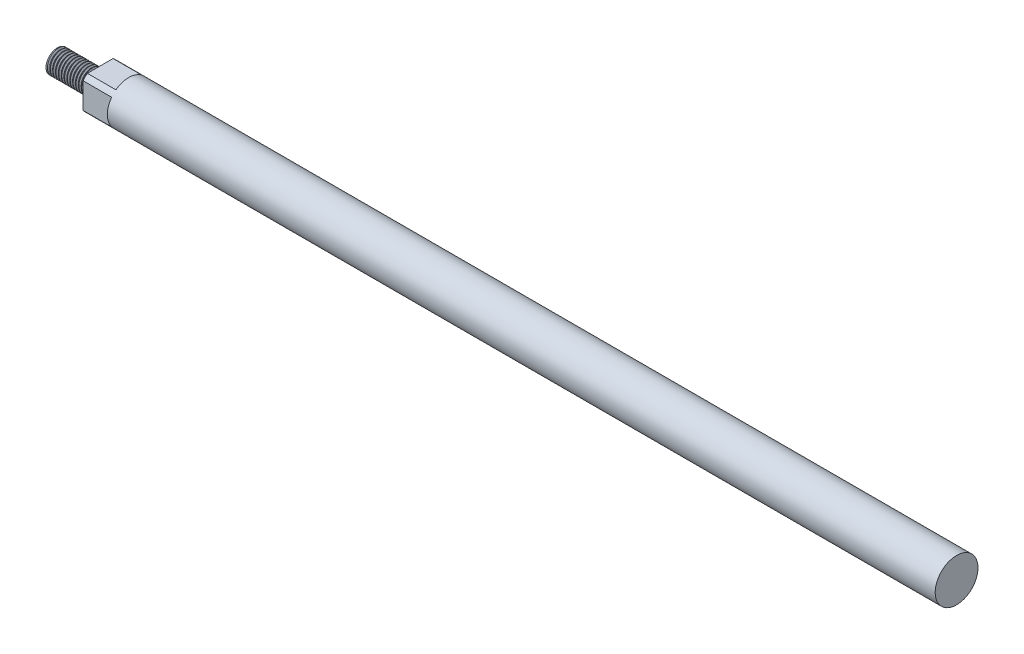
SolidWorks part; units mm, degrees
material "AISI 1045 钢，冷拔"
ref_plane "前视基准面" through (0, 0, 0) normal (0, 0, 1) x (1, 0, 0)
ref_plane "上视基准面" through (0, 0, 0) normal (0, 1, 0) x (1, 0, 0)
ref_plane "右视基准面" through (0, 0, 0) normal (1, 0, 0) x (0, 0, -1)
sketch "草图1" plane through (0, 0, 0) normal (1, 0, 0) x (0, 0, -1)
  circle A0 centre (0, 0) radius 15
  dimension "D1" = 30
extrude "凸台-拉伸1" add sketch "草图1" along normal mid plane 600
sketch "草图2" plane through (-300, 0, 0) normal (-1, 0, 0) x (0, 0, 1)
  circle A0 centre (0, 0) radius 8
  dimension "D1" = 16
extrude "凸台-拉伸2" add sketch "草图2" along normal blind 30
thread "螺纹线1" pitch 2 method cut profile "螺纹线轮廓1" start angle 0, offset 0, length 28, pitch 2, diameter 16
ref_plane "基准面1" through (-330, 0, -8) normal (0, -1, 0) x (0, 0, -1)
sketch "螺纹线轮廓1" plane through (-330, 0, -8) normal (0, -1, 0) x (0, 0, -1)
  line L0 (0, 0) -> (0, 2) construction
  line L11 (0, 0) -> (0, 1.75)
  line L12 (0, 1.75) -> (-1.0825, 1.125)
  line L13 (-1.0825, 1.125) -> (-1.0825, 0.625)
  line L15 (-1.0825, 0.625) -> (0, 0)
  line L17 (-1.0825, 0.875) -> (0, 0.875) construction
  point P2 (0, 0)
  dimension "Pitch" = 2
  dimension "Profile_Angle" = 60
  dimension "Profile_Land" = 0.5
  dimension "Profile_Height" = 1.0825
sketch "草图3" plane through (-300, 0, 0) normal (-1, 0, 0) x (0, 0, 1)
  line L1 (-12, -12) -> (12, -12)
  line L2 (-12, -12) -> (-12, 12)
  line L3 (-12, 12) -> (12, 12)
  line L4 (12, -12) -> (12, 12)
  line L5 (-12, -12) -> (12, 12) construction
  line L6 (-12, 12) -> (12, -12) construction
  point P0 (0, 0)
  dimension "D1" = 24
  dimension "D2" = 24
extrude "切除-拉伸1" cut sketch "草图3" against normal blind 20 flip side to cut
